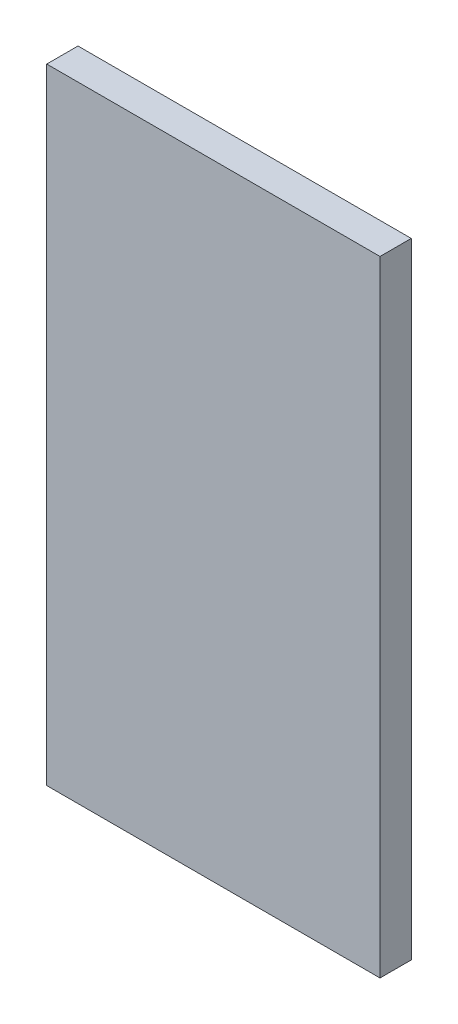
SolidWorks part; units mm, degrees
ref_plane "Спереди (XY) " through (0, 0, 0) normal (0, 0, 1) x (1, 0, 0)
ref_plane "Сверху (XZ)" through (0, 0, 0) normal (0, 1, 0) x (1, 0, 0)
ref_plane "Справа (ZY)" through (0, 0, 0) normal (1, 0, 0) x (0, 0, -1)
sketch "Эскиз1" plane through (0, 0, 0) normal (0, 0, 1) x (1, 0, 0)
  line L1 (0, 0) -> (16, 0)
  line L2 (0, 0) -> (0, 30)
  line L3 (0, 30) -> (16, 30)
  line L4 (16, 0) -> (16, 30)
  dimension "D1" = 30
  dimension "D2" = 16
extrude "Бобышка-Вытянуть1" add sketch "Эскиз1" along normal blind 1.5
equation "\"Mass_int\"= int ( ( \"SW-Масса\" + 0.005 ) * 100 ) / 100"
